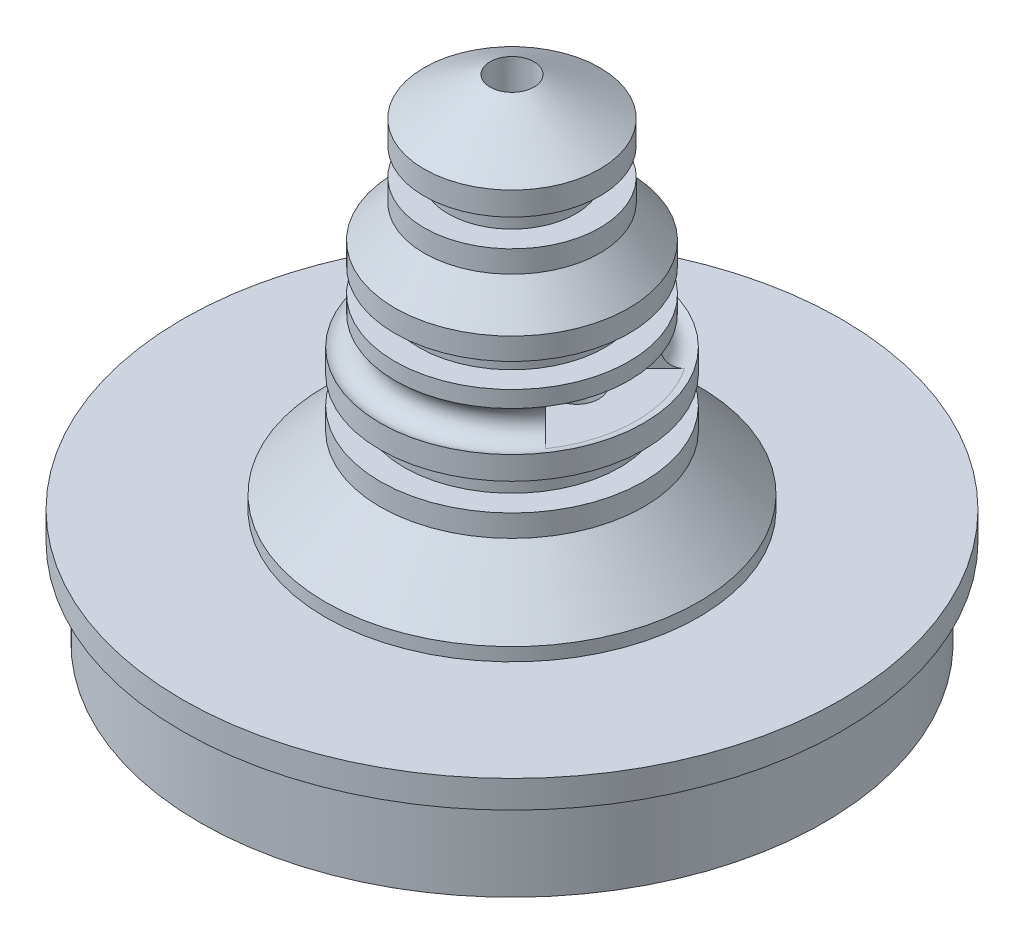
SolidWorks part; units mm, degrees
ref_plane "Спереди" through (0, 0, 0) normal (0, 0, 1) x (1, 0, 0)
ref_plane "Сверху" through (0, 0, 0) normal (0, 1, 0) x (1, 0, 0)
ref_plane "Справа" through (0, 0, 0) normal (1, 0, 0) x (0, 0, -1)
sketch "Эскиз1" plane through (0, 0, 0) normal (0, 0, 1) x (1, 0, 0)
  line L0 (0, 0) -> (0, 60) construction
  line L1 (17, 29) -> (17, 27.8)
  line L2 (2, 62.0979) -> (2, 17.3)
  line L6 (8, 56.5) -> (5.8, 56.5)
  line L7 (5.8, 56.5) -> (5.8, 54)
  line L8 (5.8, 54) -> (8, 54)
  line L10 (8, 58.6338) -> (8, 56.5)
  line L11 (8, 54) -> (8, 52)
  line L17 (10.6584, 43.2889) -> (12, 40.6056) construction
  line L19 (12, 38.5) -> (12, 40.6056)
  line L20 (12, 36) -> (9.8, 36)
  line L21 (9.8, 36) -> (9.8, 38.5)
  line L22 (9.8, 38.5) -> (12, 38.5)
  line L23 (12, 36) -> (12, 34)
  line L24 (12, 34) -> (17, 29)
  line L29 (17, 27.8) -> (30, 27.8)
  line L33 (30, 27.8) -> (30, 25.3)
  line L34 (30, 25.3) -> (28.4, 25.3)
  line L35 (28.4, 25.3) -> (28.4, 17.3)
  line L36 (28.4, 17.3) -> (2, 17.3)
  line L37 (8, 58.6338) -> (2, 62.0979)
  line L39 (10.6584, 47) -> (8.4584, 47)
  line L40 (8.4584, 47) -> (8.4584, 44.7889)
  line L41 (8.4584, 44.7889) -> (10.6584, 44.7889)
  line L42 (10.6584, 43.2889) -> (10.6584, 44.7889)
  line L43 (10.6584, 49) -> (8, 52)
  line L44 (10.6584, 47) -> (10.6584, 49)
  line L45 (11.3292, 40.4472) -> (7.0543, 40.4472) construction
  arc A3 (10.6584, 43.2889) -> (12, 40.6056) centre (11.3292, 41.9472) ccw
  point P20 (0, 0)
  point P22 (12, 43)
  point P24 (0, 0)
  dimension "D5" = 2.5
  dimension "D14" = 24
  dimension "D13" = 3
  dimension "D3" = 4
  dimension "D4" = 16
  dimension "D6" = 2
  dimension "D7" = 2.2
  dimension "D8" = 60
  dimension "D9" = 3
  dimension "D10" = 2
  dimension "D11" = 2.2
  dimension "D12" = 1.5
  dimension "D16" = 2
  dimension "D17" = 5
  dimension "D18" = 34
  dimension "D19" = 1.2
  dimension "D20" = 2.5
  dimension "D21" = 8
  dimension "D22" = 13
  dimension "D23" = 1.6
  dimension "D24" = 7.8
revolve "Повернуть1" add sketch "Эскиз1" angle 360 about L0 reverse direction yes
sketch "Эскиз3" plane through (0, 17.3, 0) normal (0, -1, 0) x (1, 0, 0)
  line L0 (50, 0) -> (-50, 0) construction
  circle A0 centre (5.9, 0) radius 2
  dimension "D1" = 4
  dimension "D2" = 5.9
ref_plane "Плоскость1" through (0, 43.2889, 0) normal (0, -1, 0) x (-1, 0, 0)
extrude "Вырез-Вытянуть1" cut sketch "Эскиз3" against normal up to surface (25.9889 mm away) up to plane "Плоскость1"
ref_plane "Плоскость2" through (0, 40.4472, 0) normal (0, -1, 0) x (-1, 0, 0)
sketch "Эскиз4" plane through (0, 43.2889, 0) normal (0, -1, 0) x (-1, 0, 0)
  line L0 (-4.4858, 1.4142) -> (-9.3981, 6.3266)
  line L1 (-5.9, 0) -> (-22.1819, 0) construction
  line L2 (-50, 0) -> (50, 0) construction
  line L3 (-4.4858, -1.4142) -> (-9.3981, -6.3266)
  circle A2 centre (-5.9, 0) radius 2 construction
  arc A3 (-4.4858, -1.4142) -> (-4.4858, 1.4142) centre (-5.9, 0) ccw
  arc A4 (-9.3981, 6.3266) -> (-9.3981, -6.3266) centre (0, 0) ccw
  point P2 (-11.3292, 0)
  point P5 (-11.3292, 0)
  dimension "D1" = 90
extrude "Вырез-Вытянуть2" cut sketch "Эскиз4" along normal up to surface (2.8416 mm away) up to plane "Плоскость2"
